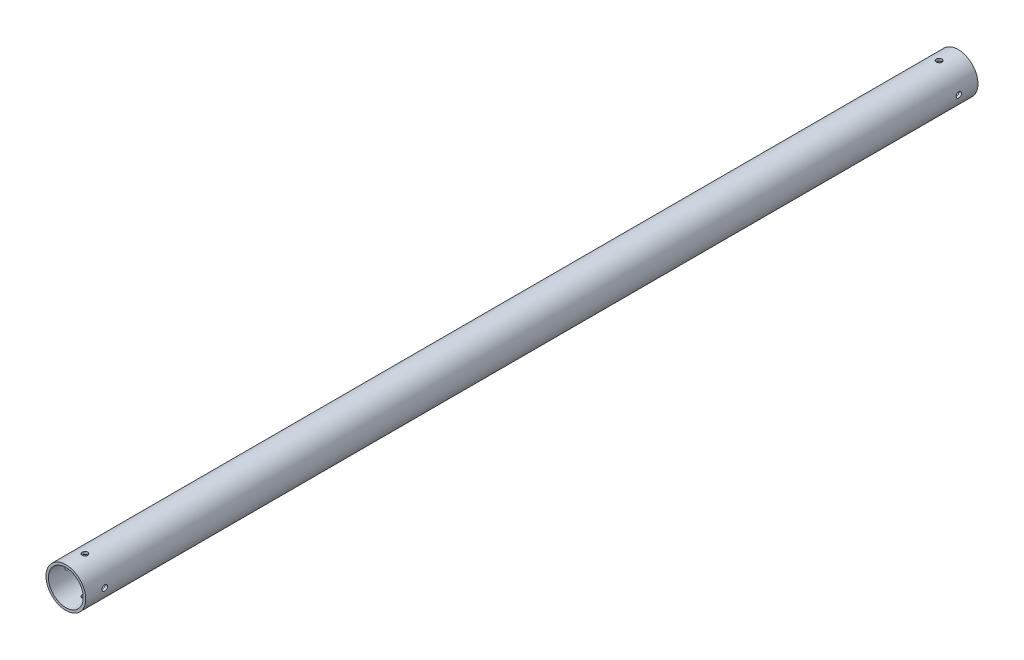
SolidWorks part; units mm, degrees
material "PC High Viscosity"
ref_plane "Front Plane" through (0, 0, 0) normal (0, 0, 1) x (1, 0, 0)
ref_plane "Top Plane" through (0, 0, 0) normal (0, 1, 0) x (1, 0, 0)
ref_plane "Right Plane" through (0, 0, 0) normal (1, 0, 0) x (0, 0, -1)
sketch "Sketch2" plane through (0, 0, 0) normal (0, 0, 1) x (1, 0, 0)
  circle A0 centre (0, 0) radius 11.1125
  circle A1 centre (0, 0) radius 12.7
  dimension "D1" = 25.4
  dimension "D2" = 22.225
extrude "Boss-Extrude1" add sketch "Sketch2" along normal mid plane 570.1883
sketch "Sketch3" plane through (0, 0, 0) normal (0, 1, 0) x (1, 0, 0)
  line L0 (-12.7, -285.0942) -> (12.7, -285.0942) construction
  line L1 (-13.97, 0) -> (13.97, 0) construction
  circle A0 centre (0, -272.9022) radius 1.7526
  circle A1 centre (0, 272.9022) radius 1.7526
  point P4 (0, 0)
  dimension "D1" = 3.5052
  dimension "D2" = 12.192
extrude "Cut-Extrude1" cut sketch "Sketch3" against normal through all both and the other way through all
sketch "Sketch4" plane through (0, 0, 0) normal (1, 0, 0) x (0, 0, -1)
  line L0 (-285.0942, 12.7) -> (-285.0942, -12.7) construction
  line L1 (0, 13.97) -> (0, -13.97) construction
  circle A0 centre (-272.9022, 0) radius 1.7526
  circle A1 centre (272.9022, 0) radius 1.7526
  point P4 (0, 0)
  dimension "D1" = 3.5052
  dimension "D2" = 12.192
extrude "Cut-Extrude2" cut sketch "Sketch4" against normal through all both and the other way through all
